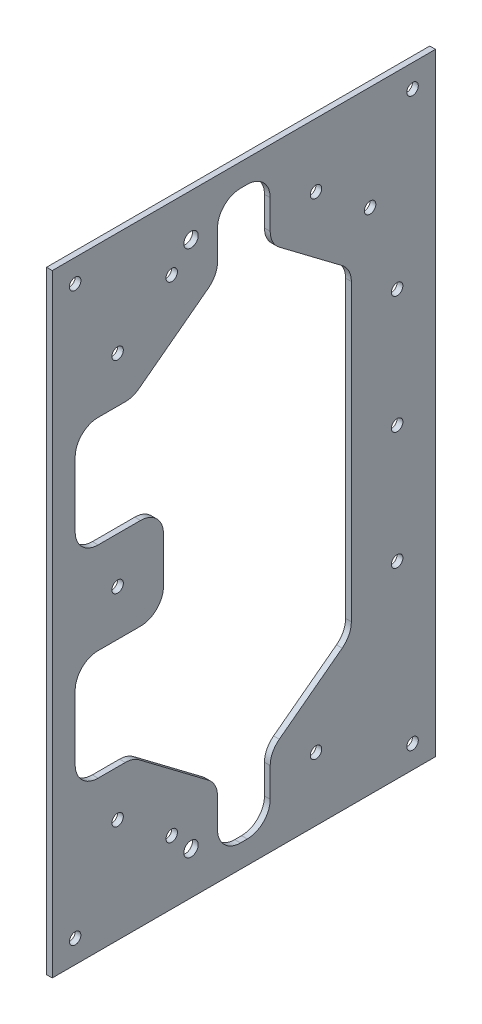
SolidWorks part; units mm, degrees
material "6061-T6 (SS)"
ref_plane "Front Plane" through (0, 0, 0) normal (0, 0, 1) x (1, 0, 0)
ref_plane "Top Plane" through (0, 0, 0) normal (0, 1, 0) x (1, 0, 0)
ref_plane "Right Plane" through (0, 0, 0) normal (1, 0, 0) x (0, 0, -1)
sketch "Sketch1" plane through (0, 0, 0) normal (1, 0, 0) x (0, 0, -1)
  line L0 (0, -169.8625) -> (212.5, -169.8625) construction
  line L1 (0, 0) -> (212.5, 0)
  line L2 (0, 0) -> (0, -339.725)
  line L3 (0, -339.725) -> (212.5, -339.725)
  line L4 (212.5, 0) -> (212.5, -339.725)
  line L5 (153.5, -35.2425) -> (59, -35.2425) construction
  line L6 (191.25, -104.5325) -> (191.25, -169.8625) construction
  line L7 (13.5, -50.2425) -> (59, -50.2425) construction
  line L8 (36.25, -50.2425) -> (36.25, -169.8625) construction
  line L9 (106.25, 0) -> (106.25, -339.725) construction
  line L10 (173.5, -104.5325) -> (191.25, -104.5325) construction
  circle A0 centre (12.7, -12.7) radius 3.175
  circle A1 centre (199.8, -12.7) radius 3.175
  circle A2 centre (66.25, -35.2425) radius 3.175
  circle A3 centre (146.25, -35.2425) radius 3.175
  circle A4 centre (176.25, -57.8625) radius 3.175
  circle A5 centre (36.25, -57.8625) radius 3.175
  circle A6 centre (191.25, -104.5325) radius 3.175
  circle A7 centre (36.25, -169.8625) radius 3.175
  circle A8 centre (191.25, -169.8625) radius 3.175
  circle A9 centre (36.25, -281.8625) radius 3.175
  circle A10 centre (66.25, -304.4825) radius 3.175
  circle A11 centre (12.7, -327.025) radius 3.175
  circle A12 centre (199.8, -327.025) radius 3.175
  circle A13 centre (146.25, -304.4825) radius 3.175
  circle A14 centre (191.25, -235.1925) radius 3.175
  dimension "D1" = 339.725
  dimension "D2" = 212.5
  dimension "D3" = 40
  dimension "D4" = 112
  dimension "D5" = 85
  dimension "D6" = 157.1625
extrude "Boss-Extrude1" add sketch "Sketch1" along normal blind 3.175
sketch "Sketch2" plane through (3.175, 0, 0) normal (1, 0, 0) x (0, 0, -1)
  line L1 (165.85, -88.1617) -> (165.85, -251.5633)
  line L4 (0, 0) -> (0, -339.725)
  line L5 (0, -339.725) -> (212.5, -339.725)
  line L6 (212.5, -339.725) -> (212.5, 0)
  line L7 (212.5, 0) -> (0, 0)
  line L8 (0, 0) -> (0, -339.725)
  line L9 (0, -339.725) -> (212.5, -339.725)
  line L10 (212.5, -339.725) -> (212.5, 0)
  line L11 (212.5, 0) -> (0, 0)
  line L14 (25.4, -144.4625) -> (48.95, -144.4625)
  line L15 (25.4, -83.2625) -> (40.5014, -83.2625)
  line L16 (12.7, -95.9625) -> (12.7, -131.7625)
  line L17 (34.7163, -60.6425) -> (37.7837, -60.6425)
  line L18 (61.65, -70.5625) -> (61.65, -70.522)
  line L19 (61.65, -182.5625) -> (61.65, -157.1625)
  line L20 (36.25, -57.8625) -> (66.25, -35.2425) construction
  line L21 (48.1473, -80.703) -> (86.5959, -51.7127)
  line L22 (91.65, -25.4) -> (91.65, -41.5722)
  line L23 (120.85, -25.4) -> (120.85, -41.5722)
  line L24 (104.35, -12.7) -> (108.15, -12.7)
  line L25 (176.25, -57.8625) -> (146.25, -35.2425) construction
  line L26 (125.9041, -51.7127) -> (160.7959, -78.0212)
  line L27 (0, -169.8625) -> (212.5, -169.8625) construction
  line L28 (176.25, -281.8625) -> (146.25, -304.4825) construction
  line L29 (36.25, -281.8625) -> (66.25, -304.4825) construction
  line L30 (125.9041, -288.0123) -> (160.7959, -261.7038)
  line L31 (104.35, -327.025) -> (108.15, -327.025)
  line L32 (120.85, -314.325) -> (120.85, -298.1528)
  line L33 (91.65, -314.325) -> (91.65, -298.1528)
  line L34 (48.1473, -259.022) -> (86.5959, -288.0123)
  line L35 (61.65, -269.1625) -> (61.65, -269.203)
  line L36 (34.7163, -279.0825) -> (37.7837, -279.0825)
  line L37 (12.7, -243.7625) -> (12.7, -207.9625)
  line L38 (25.4, -256.4625) -> (40.5014, -256.4625)
  line L39 (25.4, -195.2625) -> (48.95, -195.2625)
  circle A0 centre (176.25, -57.8625) radius 3.175 construction
  circle A1 centre (146.25, -35.2425) radius 3.175 construction
  circle A2 centre (66.25, -35.2425) radius 3.175 construction
  circle A3 centre (36.25, -57.8625) radius 3.175 construction
  circle A4 centre (36.25, -169.8625) radius 3.175 construction
  circle A5 centre (36.25, -281.8625) radius 3.175 construction
  circle A6 centre (66.25, -304.4825) radius 3.175 construction
  circle A7 centre (146.25, -304.4825) radius 3.175 construction
  circle A8 centre (191.25, -235.1925) radius 3.175 construction
  circle A9 centre (191.25, -169.8625) radius 3.175 construction
  circle A10 centre (191.25, -104.5325) radius 3.175 construction
  circle A11 centre (176.25, -57.8625) radius 3.175 construction
  circle A12 centre (146.25, -35.2425) radius 3.175 construction
  circle A13 centre (66.25, -35.2425) radius 3.175 construction
  circle A14 centre (36.25, -57.8625) radius 3.175 construction
  circle A15 centre (36.25, -169.8625) radius 3.175 construction
  circle A16 centre (36.25, -281.8625) radius 3.175 construction
  circle A17 centre (66.25, -304.4825) radius 3.175 construction
  circle A18 centre (146.25, -304.4825) radius 3.175 construction
  circle A19 centre (191.25, -235.1925) radius 3.175 construction
  circle A20 centre (191.25, -169.8625) radius 3.175 construction
  circle A21 centre (191.25, -104.5325) radius 3.175 construction
  arc A28 (48.95, -144.4625) -> (61.65, -157.1625) centre (48.95, -157.1625) cw
  arc A29 (12.7, -131.7625) -> (25.4, -144.4625) centre (25.4, -131.7625) ccw
  arc A30 (12.7, -95.9625) -> (25.4, -83.2625) centre (25.4, -95.9625) cw
  arc A33 (165.85, -88.1617) -> (160.7959, -78.0212) centre (153.15, -88.1617) ccw
  arc A34 (125.9041, -51.7127) -> (120.85, -41.5722) centre (133.55, -41.5722) cw
  arc A35 (108.15, -12.7) -> (120.85, -25.4) centre (108.15, -25.4) cw
  arc A36 (104.35, -12.7) -> (91.65, -25.4) centre (104.35, -25.4) ccw
  arc A37 (86.5959, -51.7127) -> (91.65, -41.5722) centre (78.95, -41.5722) ccw
  arc A38 (48.1473, -80.703) -> (40.5014, -83.2625) centre (40.5014, -70.5625) cw
  circle A39 centre (36.25, -281.8625) radius 3.175 construction
  circle A40 centre (66.25, -304.4825) radius 3.175 construction
  circle A41 centre (146.25, -304.4825) radius 3.175 construction
  circle A42 centre (176.25, -281.8625) radius 3.175 construction
  arc A43 (48.1473, -259.022) -> (40.5014, -256.4625) centre (40.5014, -269.1625) ccw
  arc A44 (86.5959, -288.0123) -> (91.65, -298.1528) centre (78.95, -298.1528) cw
  arc A45 (104.35, -327.025) -> (91.65, -314.325) centre (104.35, -314.325) cw
  arc A46 (108.15, -327.025) -> (120.85, -314.325) centre (108.15, -314.325) ccw
  arc A47 (125.9041, -288.0123) -> (120.85, -298.1528) centre (133.55, -298.1528) ccw
  arc A48 (165.85, -251.5633) -> (160.7959, -261.7038) centre (153.15, -251.5633) cw
  arc A49 (12.7, -243.7625) -> (25.4, -256.4625) centre (25.4, -243.7625) ccw
  arc A50 (12.7, -207.9625) -> (25.4, -195.2625) centre (25.4, -207.9625) cw
  arc A51 (48.95, -195.2625) -> (61.65, -182.5625) centre (48.95, -182.5625) ccw
  point P73 (61.65, -83.2625)
  point P78 (61.65, -60.6425)
  point P92 (61.65, -279.0825)
  point P110 (61.65, -169.8625)
  point P114 (165.85, -169.8625)
  point P115 (61.65, -256.4625)
  dimension "D11" = 25.4
  dimension "D13" = 25.4
  dimension "D17" = 12.7
  dimension "D2" = 25.4
  dimension "D7" = 25.4
  dimension "D8" = 25.4
  dimension "D9" = 25.4
  dimension "D14" = 25.4
  dimension "D15" = 12.7
  dimension "D16" = 25.4
  dimension "D1" = 0
extrude "Cut-Extrude1" cut sketch "Sketch2" against normal through all contours L1 L18 L15 A30 L16 A29 L14 A28 L19 A43 region at (3.175, -169.8625, -97.6088)
sketch "Sketch3" plane through (0, 0, 0) normal (-1, 0, 0) x (0, 0, 1)
  line L0 (-99.95, -11.9115) -> (-99.95, -342.1115) construction
  line L1 (-99.95, -11.9115) -> (-99.95, -342.1115)
  line L3 (-303.15, -342.1115) -> (-99.95, -342.1115) construction
  circle A0 centre (-76.95, -316.1115) radius 4
  dimension "D2" = 26
  dimension "D3" = 8
  dimension "D1" = 23
extrude "Cut-Extrude2" cut sketch "Sketch3" against normal blind 45.72 contours A0
sketch "Sketch4" plane through (0, 0, 0) normal (-1, 0, 0) x (0, 0, 1)
  circle A0 centre (-76.9625, -23.6135) radius 4 construction
  circle A1 centre (-76.9625, -23.6135) radius 4
extrude "Cut-Extrude3" cut sketch "Sketch4" against normal blind 14.986
